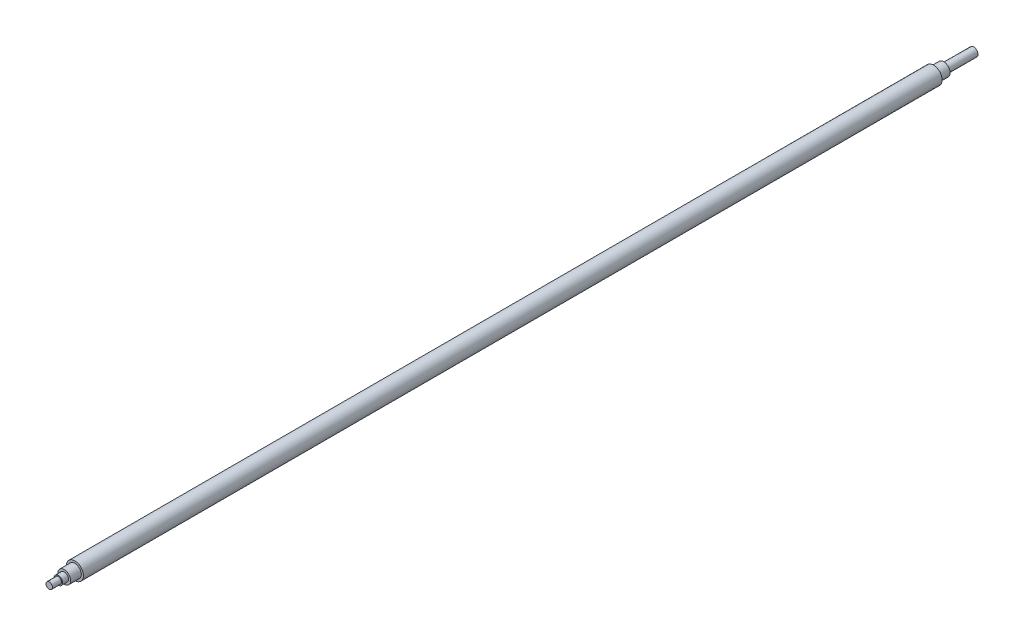
SolidWorks part; units mm, degrees
ref_plane "Piano frontale" through (0, 0, 0) normal (0, 0, 1) x (1, 0, 0)
ref_plane "Piano superiore" through (0, 0, 0) normal (0, 1, 0) x (1, 0, 0)
ref_plane "Piano destro" through (0, 0, 0) normal (1, 0, 0) x (0, 0, -1)
sketch "Schizzo2" plane through (0, 0, 0) normal (1, 0, 0) x (0, 0, -1)
  line L0 (0, 0) -> (0, 3)
  line L1 (0, 3) -> (8.5, 3)
  line L2 (8.5, 3) -> (8.5, 4)
  line L3 (8.5, 4) -> (14, 4)
  line L4 (14, 4) -> (14, 6)
  line L5 (14, 6) -> (24, 6)
  line L6 (24, 6) -> (24, 8)
  line L7 (24, 8) -> (826, 8)
  line L8 (826, 8) -> (826, 6)
  line L9 (826, 6) -> (835.5, 6)
  line L10 (835.5, 6) -> (835.5, 4)
  line L11 (863.5, 0) -> (0, 0)
  line L14 (863.5, 0) -> (863.5, 4)
  line L15 (0, 0) -> (351.0218, 0) construction
  line L18 (835.5, 4) -> (863.5, 4)
  point P33 (0, 0)
  dimension "D2" = 6
  dimension "D3" = 8
  dimension "D4" = 12
  dimension "D5" = 16
  dimension "D6" = 12
  dimension "D7" = 8
  dimension "D8" = 8.5
  dimension "D9" = 5.5
  dimension "D10" = 10
  dimension "D11" = 802
  dimension "D12" = 9.5
  dimension "D13" = 28
revolve "Rivoluzione2" add sketch "Schizzo2" angle 360 about L15
